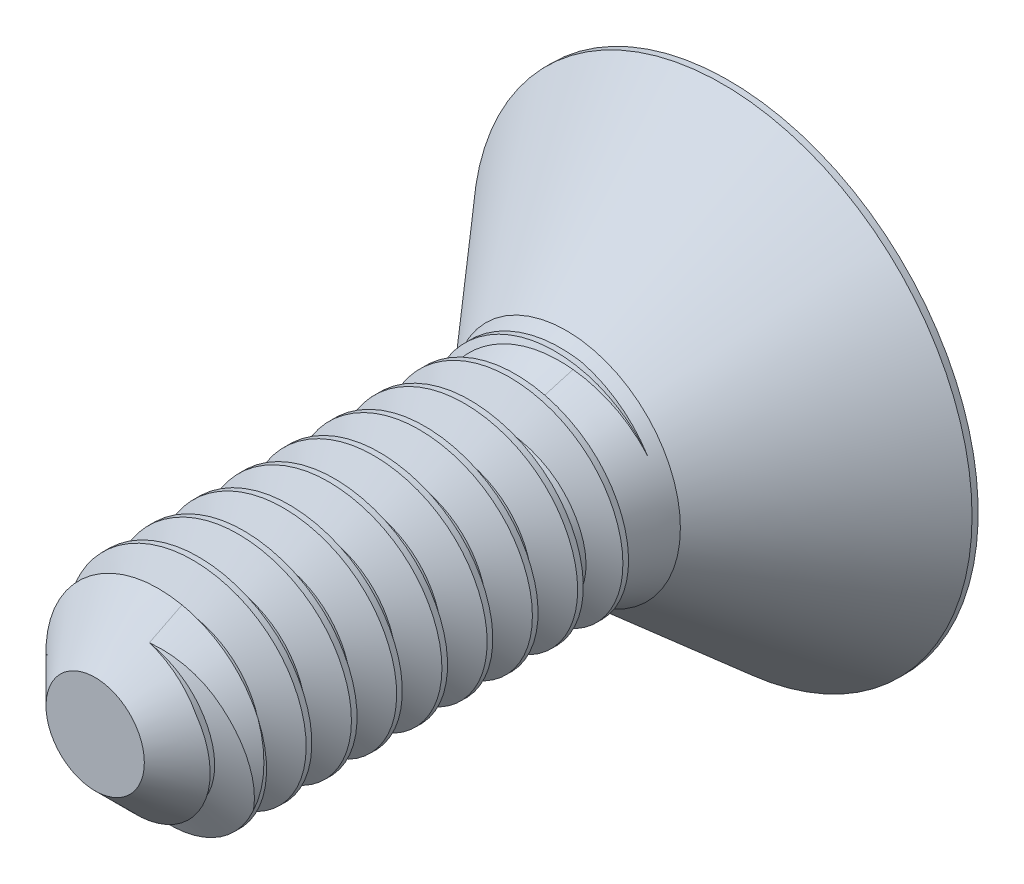
SolidWorks part; units mm, degrees
ref_plane "Front Plane" through (0, 0, 0) normal (0, 0, 1) x (1, 0, 0)
ref_plane "Top Plane" through (0, 0, 0) normal (0, 1, 0) x (1, 0, 0)
ref_plane "Right Plane" through (0, 0, 0) normal (1, 0, 0) x (0, 0, -1)
sketch "Sketch1" plane through (0, 0, 0) normal (0, 0, 1) x (1, 0, 0)
  circle A0 centre (0, 0) radius 1.0922
  dimension "OD" = 2.1844
extrude "Extrude1" add sketch "Sketch1" against normal blind 6.35
sketch "Sketch2" plane through (0, 0, 0) normal (0, 0, 1) x (1, 0, 0)
  circle A0 centre (0, 0) radius 1.0922 construction
  circle A1 centre (0, 0) radius 1.0922
curve "Helix/Spiral1" pitch 0.4536 height 6.8036 radius 1.0922 centre (0, 0, 0) axis (0, 0, -1) start towards (0, 1, 0) parameters "pitch"=0.4536
sketch "Sketch3" plane through (0, 0, 0) normal (1, 0, 0) x (0, 0, -1)
  line L0 (-0.3969, 1.0922) -> (-0.2268, 0.7976)
  line L1 (-0.2268, 0.7976) -> (-0.1701, 0.7976)
  line L2 (-0.1701, 0.7976) -> (0, 1.0922)
  line L3 (-0.3969, 1.0922) -> (0, 1.0922)
  line L4 (-0.1984, 1.0922) -> (-0.1984, 0.7976) construction
  line L5 (-0.3118, 0.9449) -> (-0.085, 0.9449) construction
  line L6 (0, 1.0922) -> (0, -1.0922) construction
  dimension "D1" = 0.0567
  dimension "D2" = 0.2268
  dimension "D3" = 60
sweep "Cut-Sweep1" cut profiles "Sketch3" path "Helix/Spiral1"
sketch "Sketch4" plane through (0, 0, 0) normal (1, 0, 0) x (0, 0, -1)
  line L0 (0.5994, 1.0922) -> (0, 0.4928)
  line L1 (0, 0.4928) -> (0, 1.0922)
  line L2 (0.5994, 1.0922) -> (0, 1.0922)
  line L3 (-0.3969, 1.0922) -> (0, 1.0922) construction
  line L4 (0, 0) -> (7.0209, 0) construction
  dimension "D1" = 45
  dimension "D2" = 0.3048
revolve "Cut-Revolve1" cut sketch "Sketch4" angle 360 about L4
sketch "Sketch5" plane through (0, 0, 0) normal (1, 0, 0) x (0, 0, -1)
  line L0 (6.35, -0.8061) -> (6.35, 0.7793) construction
  line L1 (6.35, 1.1422) -> (38.2906, 1.1422)
  line L2 (6.35, 1.1422) -> (6.35, 0)
  line L3 (6.35, 0) -> (38.1, 0)
  line L4 (38.1, 0.812) -> (38.1, 0)
  line L5 (38.2906, 1.1422) -> (38.1, 0.812)
  line L6 (0, 0) -> (9.9695, 0) construction
  point P3 (38.1, 1.1422)
  point P10 (38.1, 1.1422)
  dimension "D1" = 0.3302
  dimension "Thread min" = 38.1
  dimension "D2" = 0.05
  dimension "D3" = 30
revolve "partially thread" [suppressed] add sketch "Sketch5" angle 360 about L6
sketch "Sketch6" plane through (0, 0, -6.35) normal (0, 0, -1) x (-1, 0, 0)
  circle A0 centre (0, 0) radius 2.5019
  dimension "head dia" = 5.0038
extrude "Extrude2" add sketch "Sketch6" against normal blind 1.6256
sketch "Sketch10" plane through (0, 0, 0) normal (1, 0, 0) x (0, 0, -1)
  line L0 (6.2886, -2.5019) -> (4.7244, -1.1422)
  line L1 (4.7244, -1.1422) -> (4.7244, -2.5019)
  line L2 (6.2886, -2.5019) -> (4.7244, -2.5019)
  line L3 (0, 0) -> (4.7244, 0) construction
  line L4 (4.7244, 2.5019) -> (4.7244, -2.5019) construction
  line L5 (6.2886, 2.5019) -> (4.7244, 2.5019) construction
  line L6 (4.7244, 1.1422) -> (4.7244, 2.5019) construction
  line L7 (6.2886, 2.5019) -> (4.7244, 1.1422) construction
  line L8 (4.7244, 2.5019) -> (4.7244, -2.5019) construction
  line L9 (4.7244, 1.1422) -> (4.7244, -1.1422) construction
  dimension "D1" = 41
  dimension "D2" = 0.05
revolve "Cut-Revolve2" cut sketch "Sketch10" angle 360 about L3
sketch "Sketch11" plane through (0, 0, 0) normal (1, 0, 0) x (0, 0, -1)
  line L0 (4.7244, -1.1422) -> (3.9319, -0.7976)
  line L2 (4.7244, -1.1422) -> (4.7244, -2.5019) construction
  line L3 (4.7244, -1.1422) -> (4.7244, 0)
  line L4 (3.9319, 0) -> (4.7244, 0)
  line L5 (3.9319, 0) -> (3.9319, -0.7976)
  line L6 (0, 0) -> (4.7244, 0) construction
  line L7 (0, 0.7976) -> (0, -0.7976) construction
  dimension "D1" = 23.5
revolve "Revolve1" add sketch "Sketch11" angle 360 about L3
sketch "Sketch7" plane through (0, 0, -6.35) normal (0, 0, 1) x (1, 0, 0)
  line L1 (0, 0.7332) -> (-0.635, 0.3666)
  line L2 (-0.635, 0.3666) -> (-0.635, -0.3666)
  line L3 (-0.635, -0.3666) -> (0, -0.7332)
  line L4 (0, -0.7332) -> (0.635, -0.3666)
  line L5 (0.635, -0.3666) -> (0.635, 0.3666)
  line L6 (0.635, 0.3666) -> (0, 0.7332)
  circle A0 centre (0, 0) radius 0.635 construction
  dimension "hex dia" = 1.27
extrude "Cut-Extrude1" cut sketch "Sketch7" along normal blind 0.9525
sketch "Sketch8" plane through (0, 0, -6.35) normal (0, 0, 1) x (1, 0, 0)
  circle A0 centre (0, 0) radius 0.7332
extrude "Cut-Extrude2" cut sketch "Sketch8" along normal through all draft 45
sketch "Sketch9" plane through (0, 0, 0) normal (1, 0, 0) x (0, 0, -1)
  line L0 (0, 1.0922) -> (0, -1.0922) construction
  line L1 (2.4946, 1.0922) -> (2.4946, -1.0922) construction
  line L2 (4.7244, 1.0922) -> (4.7244, -1.0922) construction
  line L3 (4.7244, -1.1422) -> (4.7244, -2.5019) construction
  dimension "D1" = 2.4946
equation "\"D3@Helix/Spiral1\" = \"screw length@Extrude1\"+\"pitch@Helix/Spiral1\""
equation "\"D1@Sketch3\" = \"pitch@Helix/Spiral1\"*.125"
equation "\"D2@Sketch3\" = \"pitch@Helix/Spiral1\"*.5"
equation "\"D1@Cut-Extrude1\" = \"hex dia@Sketch7\"*.75"
equation "\"D1@Sketch9\" = \"pitch@Helix/Spiral1\"*5.5"
equation "\"D2@Sketch10\" = \"D2@Sketch5\""
